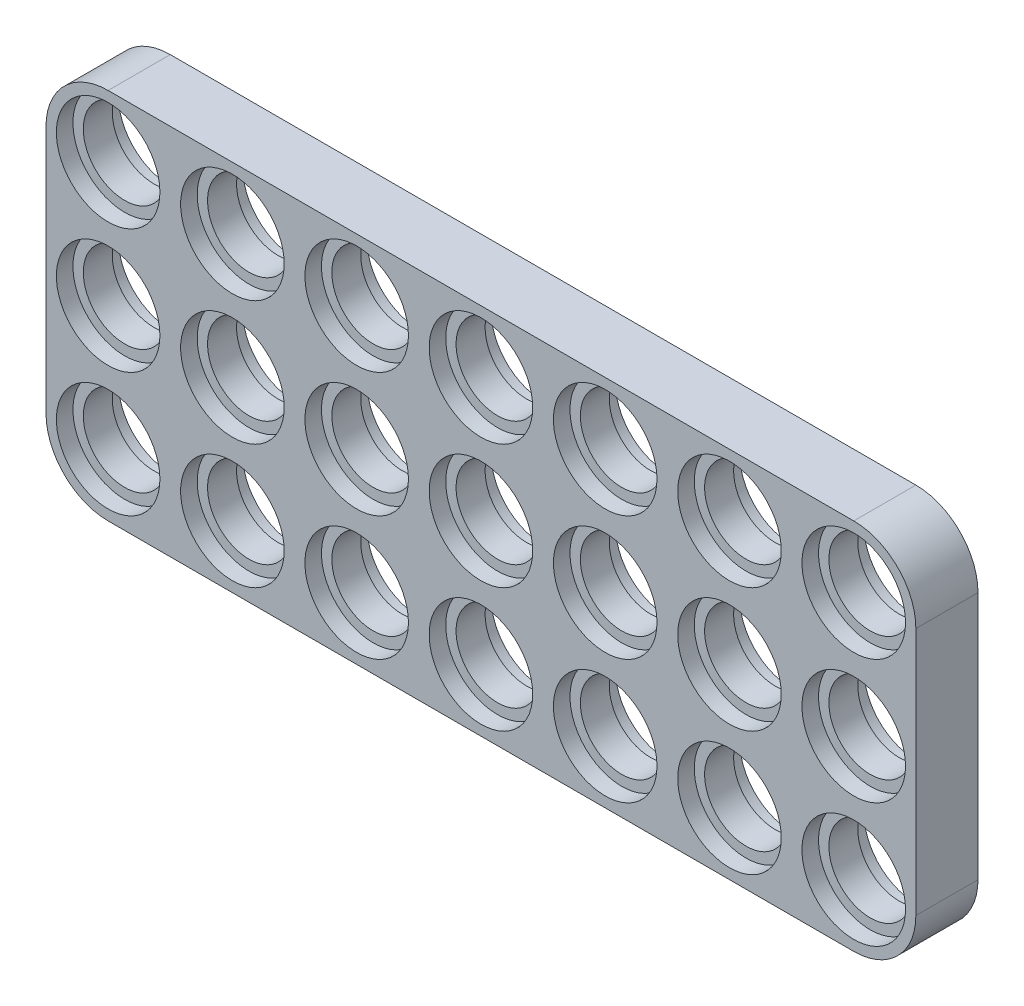
SolidWorks part; units mm, degrees
material "ABS"
ref_plane "Plan de face" through (0, 0, 0) normal (0, 0, 1) x (1, 0, 0)
ref_plane "Plan de dessus" through (0, 0, 0) normal (0, 1, 0) x (1, 0, 0)
ref_plane "Plan de droite" through (0, 0, 0) normal (1, 0, 0) x (0, 0, -1)
sketch "Sketch1" plane through (0, 0, 0) normal (0, 0, 1) x (1, 0, 0)
  line L1 (0, 0) -> (-6, 0)
  line L2 (0, 0) -> (0, 6)
  line L3 (0, 6) -> (-6, 6)
  line L4 (-6, 0) -> (-6, 6)
  dimension "D1" = 6
  dimension "D2" = 6
extrude "Boss-Extrude1" add sketch "Sketch1" along normal blind 3
hole_wizard "Hole1" positions "Sketch3" profile "Sketch2" legacy end condition through all
sketch "Sketch3" plane through (0, 0, 3) normal (0, 0, 1) x (1, 0, 0)
  line L0 (-6, 6) -> (0, 0) construction
  point P0 (-3, 3)
sketch "Sketch2" plane through (-3, 3, 3) normal (1, 0, 0) x (0, -1, 0)
  line L0 (0, 0) -> (0, 4.2017)
  line L1 (0, 4.2017) -> (2, 3)
  line L2 (2, 3) -> (2, 0.8)
  line L3 (2, 0.8) -> (2.5, 0.8)
  line L4 (2.5, 0) -> (0, 0)
  line L5 (0, -11.3109) -> (0, 121.1557) construction
  line L6 (0, 4.2017) -> (-2, 3) construction
  line L7 (2.5, 0.8) -> (2.5, 0)
  dimension "Depth" = 3
  dimension "Drill Angle" = 118
  dimension "Diameter" = 4
  dimension "C-Bore Diameter" = 5
  dimension "C-Bore Depth" = 0.8
sketch "Sketch4" plane through (0, 0, 0) normal (0, 0, -1) x (-1, 0, 0)
  circle A0 centre (3, 3) radius 2.5
  dimension "D1" = 5
extrude "Cut-Extrude1" cut sketch "Sketch4" against normal blind 0.8
pattern_linear "LPattern1" count 3 spacing 6 along (0, 1, 0) count 7 spacing 6 along (1, 0, 0) of "Boss-Extrude1"
combine bodies "Combine1" [suppressed] operation type add bodies to combine 117 103 104 105 106 107 108 109 110 111 112 113 114 115 116
combine bodies "Combine2" [suppressed] operation type add bodies to combine 103 104 105 105 106 107 109 108 109 110 113 111 112 113 119 114 115 116 123 117
fillet "Fillet1" [suppressed] radius 3
fillet "Fillet3" [suppressed] radius 3
fillet "Fillet4" [suppressed] radius 3
combine bodies "Combine3" operation type add bodies to combine 117 103 104 105 106 107 108 109 110 111 112 113 114 115 116 119 120 121 122 123 125
fillet "Fillet5" radius 3 4 edges at (-6, 0, 1.5) (-6, 18, 1.5) (36, 0, 1.5) (36, 18, 1.5)
